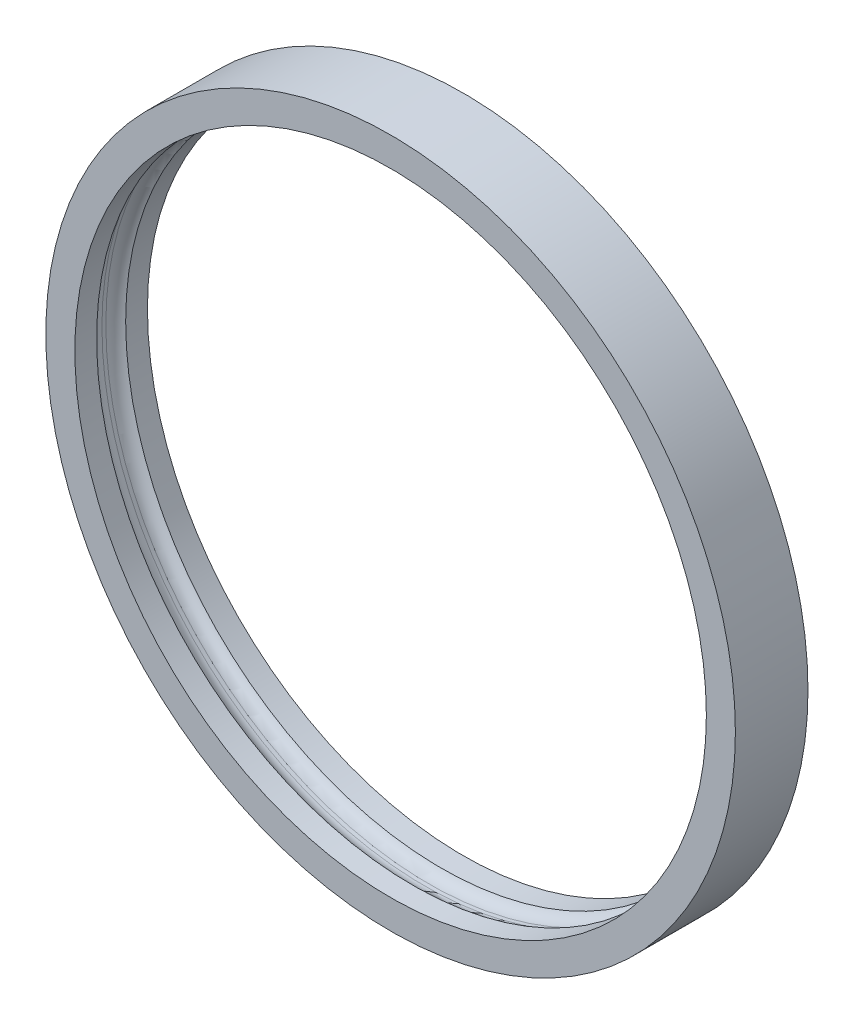
SolidWorks part; units mm, degrees
ref_plane "前视基准面" through (0, 0, 0) normal (0, 0, 1) x (1, 0, 0)
ref_plane "上视基准面" through (0, 0, 0) normal (0, 1, 0) x (1, 0, 0)
ref_plane "右视基准面" through (0, 0, 0) normal (1, 0, 0) x (0, 0, -1)
sketch "草图1" plane through (0, 0, 0) normal (0, 0, 1) x (1, 0, 0)
  circle A0 centre (0, 0) radius 47.5
  circle A1 centre (0, 0) radius 44.5
extrude "凸台-拉伸2" add sketch "草图1" along normal blind 10
sketch "草图2" plane through (0, 0, 10) normal (0, 0, 1) x (1, 0, 0)
  circle A0 centre (0, 0) radius 44.5
  circle A1 centre (0, 0) radius 43.5
extrude "凸台-拉伸3" add sketch "草图2" against normal blind 3
fillet "圆角1" radius 2 1 edges at (44.5, 0, 7)
sketch "草图3" plane through (0, 0, 0) normal (0, 0, -1) x (-1, 0, 0)
  circle A0 centre (0, 0) radius 44.5
  circle A1 centre (0, 0) radius 43.5
extrude "凸台-拉伸4" add sketch "草图3" against normal blind 3
fillet "圆角2" radius 2 1 edges at (-44.5, 0, 3)
